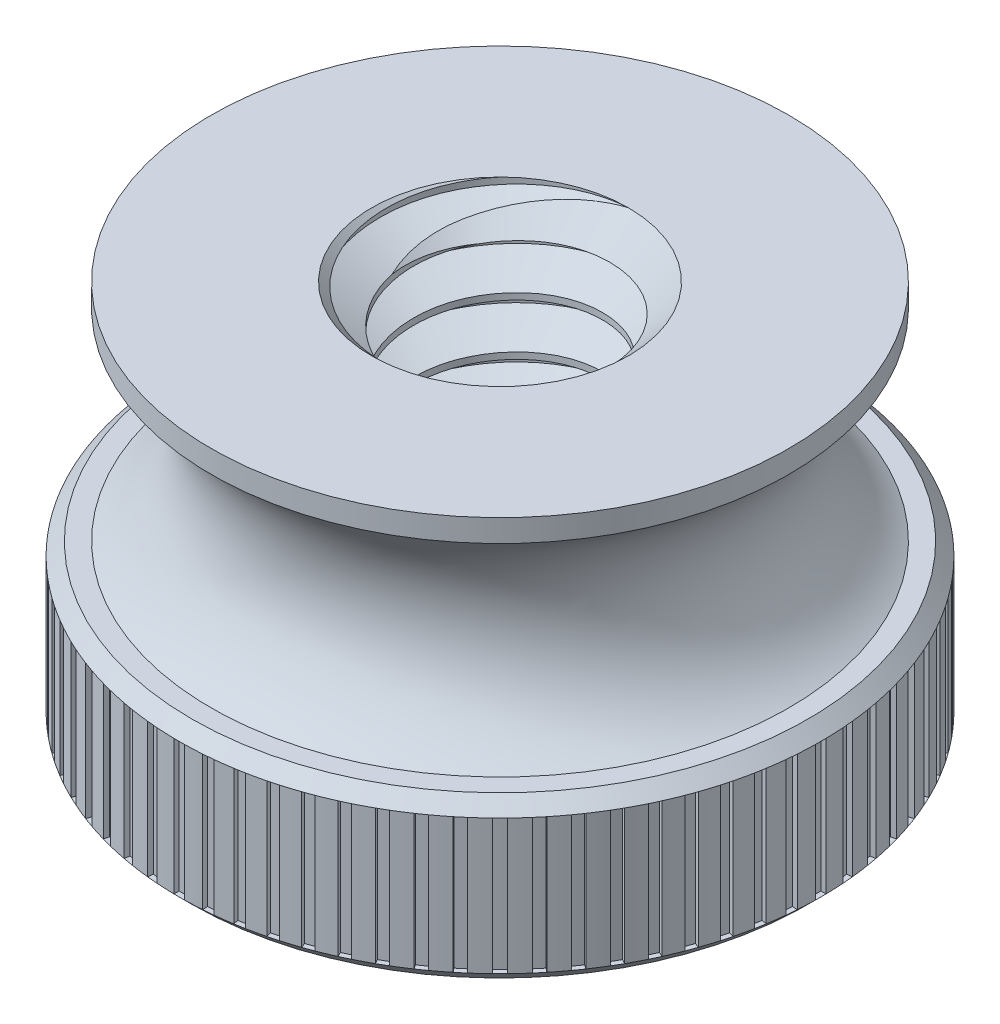
SolidWorks part; units mm, degrees
ref_plane "Front Plane" through (0, 0, 0) normal (0, 0, 1) x (1, 0, 0)
ref_plane "Top Plane" through (0, 0, 0) normal (0, 1, 0) x (1, 0, 0)
ref_plane "Right Plane" through (0, 0, 0) normal (1, 0, 0) x (0, 0, -1)
sketch "Sketch1" plane through (0, 0, 0) normal (0, 0, 1) x (1, 0, 0)
  line L0 (0, 0) -> (0, 9.525) construction
  line L1 (0, 9.525) -> (-7.1438, 9.525)
  line L2 (-7.9375, 3.9688) -> (-7.9375, 0)
  line L3 (-7.9375, 0) -> (0, 0)
  line L4 (0, 0) -> (0, 9.525)
  line L5 (0, 0) -> (0, -2.6189) construction
  line L6 (-5.715, 3.9688) -> (-5.715, 9.525) construction
  line L7 (-7.9375, 3.9688) -> (-7.1438, 3.9688)
  line L10 (-7.1438, 9.525) -> (-7.1438, 8.9694)
  arc A0 (-7.1438, 3.9688) -> (-7.1438, 8.9694) centre (-8.6171, 6.4691) ccw
  point P1 (0, 4.7625)
  dimension "D1" = 0.5556
  dimension "A" = 15.875
  dimension "D2" = 1.4287
  dimension "B" = 9.525
  dimension "C" = 14.2875
  dimension "D" = 5.5562
revolve "Revolve1" add sketch "Sketch1" angle 360 about L0
sketch "Sketch3" plane through (0, 0, 0) normal (0, 1, 0) x (1, 0, 0)
  circle A0 centre (0, 0) radius 3.175
  dimension "OD" = 6.35
extrude "Cut-Extrude1" cut sketch "Sketch3" along normal through all
sketch "Sketch4" plane through (0, 0, 0) normal (0, 1, 0) x (1, 0, 0)
  circle A1 centre (0, 0) radius 3.175
  circle A2 centre (0, 0) radius 3.175
  dimension "D1" = 0
curve "Helix/Spiral1" pitch 1.27 height 15.875 turns 12.5 parameters "pitch"=1.27
sketch "Sketch21" plane through (0, 0, 0) normal (0, 1, 0) x (1, 0, 0)
  line L0 (0, 3.175) -> (0, 7.9375)
  circle A0 centre (0, 0) radius 7.9375 construction
  circle A1 centre (0, 0) radius 3.175 construction
  circle A2 centre (0, 0) radius 7.9375 construction
  circle A3 centre (0, 0) radius 3.175 construction
  dimension "D1" = 4.7625
sketch "Sketch5" plane through (0, 0, 0) normal (1, 0, 0) x (0, 0, -1)
  line L0 (-3.175, 0) -> (-3.175, -1.1113)
  line L1 (-3.175, -1.1113) -> (-2.3501, -0.635)
  line L2 (-2.3501, -0.635) -> (-2.3501, -0.4763)
  line L3 (-2.3501, -0.4763) -> (-3.175, 0)
  line L4 (-2.3501, -0.5556) -> (-3.175, -0.5556) construction
  line L5 (-2.7626, -0.8731) -> (-2.7626, -0.2381) construction
  line L6 (3.175, 0) -> (-3.175, 0) construction
  dimension "D1" = 0.1588
  dimension "D2" = 0.635
  dimension "D3" = 60
sweep "Sweep1" add profiles "Sketch5" path "Helix/Spiral1"
sketch "Sketch13" plane through (0, 0, 0) normal (0, -1, 0) x (1, 0, 0)
  circle A1 centre (0, 0) radius 7.9375
  circle A2 centre (0, 0) radius 7.9375
  dimension "D1" = 0
extrude "Cut-Extrude2" cut sketch "Sketch13" along normal through all
sketch "Sketch14" plane through (0, 9.525, 0) normal (0, 1, 0) x (1, 0, 0)
  circle A0 centre (0, 0) radius 7.9375 construction
  circle A1 centre (0, 0) radius 7.9375
extrude "Cut-Extrude3" cut sketch "Sketch14" along normal through all
sketch "Sketch15" plane through (0, 0, 0) normal (0, -1, 0) x (1, 0, 0)
  circle A0 centre (0, 0) radius 3.175 construction
  circle A1 centre (0, 0) radius 3.175
extrude "Cut-Extrude4" cut sketch "Sketch15" against normal through all draft 45
sketch "Sketch16" plane through (0, 9.525, 0) normal (0, 1, 0) x (1, 0, 0)
  circle A0 centre (0, 0) radius 3.175 construction
  circle A1 centre (0, 0) radius 3.175
extrude "Cut-Extrude5" cut sketch "Sketch16" against normal through all draft 45
chamfer "Chamfer1" distance 0.3175 angle 45 2 edges at (0, 3.9688, -7.9375) (0, 0, -7.9375)
sketch "Sketch11" plane through (0, 0, 0) normal (0, 0, 1) x (1, 0, 0)
  line L0 (-3.175, 9.525) -> (-3.175, 0)
  line L1 (3.175, 9.525) -> (3.175, 0)
  line L2 (7.1438, 9.525) -> (-7.1438, 9.525) construction
  line L4 (-3.175, 0) -> (3.175, 0) construction
  dimension "D1" = 6.35
sketch "Sketch12" plane through (0, 0, 0) normal (1, 0, 0) x (0, 0, -1)
  line L0 (-3.175, 9.525) -> (-3.175, 0)
  line L1 (3.175, 9.525) -> (3.175, 0)
  line L2 (-3.175, 0) -> (3.175, 0) construction
  line L3 (7.1438, 9.525) -> (-7.1438, 9.525) construction
  line L5 (-7.62, 0) -> (7.62, 0) construction
  dimension "D1" = 6.35
ref_plane "Plane1" through (0, 0, -12.7) normal (0, 0, 1) x (1, 0, 0)
sketch "Sketch17" plane through (0, 0, -12.7) normal (0, 0, 1) x (1, 0, 0)
  line L0 (-0.127, 0.3175) -> (-0.127, 3.6512)
  line L1 (7.9375, 0.3175) -> (-7.9375, 0.3175) construction
  line L2 (7.9375, 3.6512) -> (-7.9375, 3.6512) construction
  line L3 (0.127, 0.3175) -> (0.127, 3.6512)
  line L4 (0, 0.3175) -> (0, 3.6512) construction
  line L5 (-0.127, 0.3175) -> (0.127, 0.3175)
  line L6 (-0.127, 3.6512) -> (0.127, 3.6512)
  line L7 (0, 1.9844) -> (6.048, 1.9844) construction
  line L8 (0, 1.9844) -> (0, 0) construction
  dimension "D1" = 0
  dimension "D2" = 0.254
extrude "Cut-Extrude6" cut sketch "Sketch17" along normal offset from surface (4.8905 mm away) 0.127 up to face at (0, 3.6512, -7.9375) offset beyond the face yes
pattern_circular "CirPattern1" count 72 over 360 about axis through (0, 0, 0) along (0, 1, 0) of "Cut-Extrude6"
sketch "Sketch18" plane through (0, 9.525, 0) normal (0, 1, 0) x (1, 0, 0)
  circle A0 centre (0, 0) radius 7.9375
  arc A2 (2.1768, 7.6332) -> (1.9314, 7.6989) centre (0, 0) ccw construction
ref_plane "Plane3" through (0, 4.7625, 0) normal (0, 1, 0) x (-1, 0, 0)
equation "\"D1@Sketch5\" = \"pitch@Helix/Spiral1\"*.125"
equation "\"D2@Sketch5\" = \"pitch@Helix/Spiral1\"*.5"
equation "\"D1@Sketch11\" = \"OD@Sketch3\""
equation "\"D1@Sketch12\" = \"OD@Sketch3\""
equation "\"D1@Chamfer1\" = \"pitch@Helix/Spiral1\"*.25"
equation "\"D3@Helix/Spiral1\" = \"B@Sketch1\"+.250"
equation "\"D1@Sketch1\" = \"D@Sketch1\"/10"
equation "\"D2@Sketch1\" = \"C@Sketch1\"*.1"
